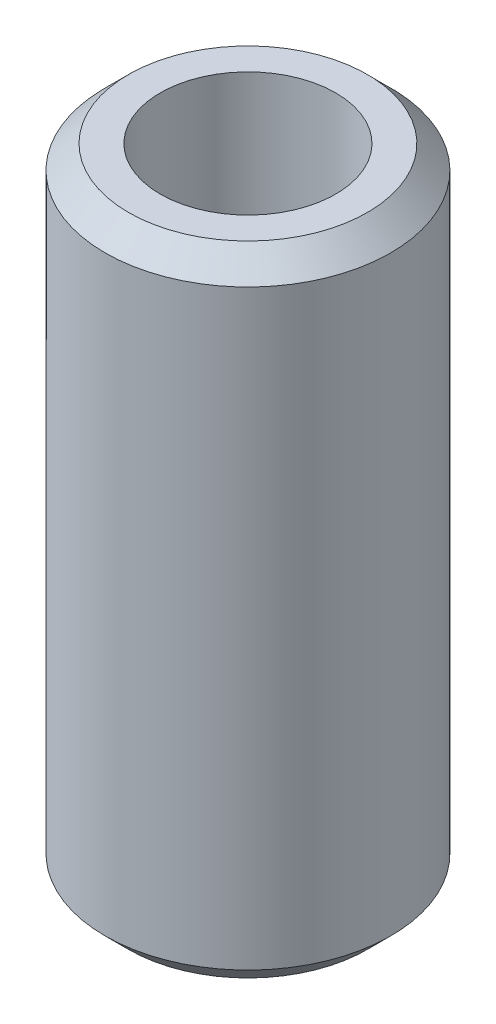
SolidWorks part; units mm, degrees
ref_plane "Front Plane" through (0, 0, 0) normal (0, 0, 1) x (1, 0, 0)
ref_plane "Top Plane" through (0, 0, 0) normal (0, 1, 0) x (1, 0, 0)
ref_plane "Right Plane" through (0, 0, 0) normal (1, 0, 0) x (0, 0, -1)
sketch "Sketch1" plane through (0, 0, 0) normal (0, 1, 0) x (1, 0, 0)
  circle A0 centre (0, 0) radius 30
  dimension "SHAFT_OD" = 60
extrude "Boss-Extrude1" add sketch "Sketch1" along normal blind 134.0657
sketch "Sketch2" plane through (0, 0, 0) normal (0, 1, 0) x (1, 0, 0)
  circle A0 centre (0, 0) radius 18.4316
  dimension "BORE_D" = 36.8631
extrude "Cut-Extrude1" cut sketch "Sketch2" along normal through all
chamfer "Chamfer1" distance 4.902 angle 45 2 edges at (0, 134.0657, 30) (0, 0, 30)
